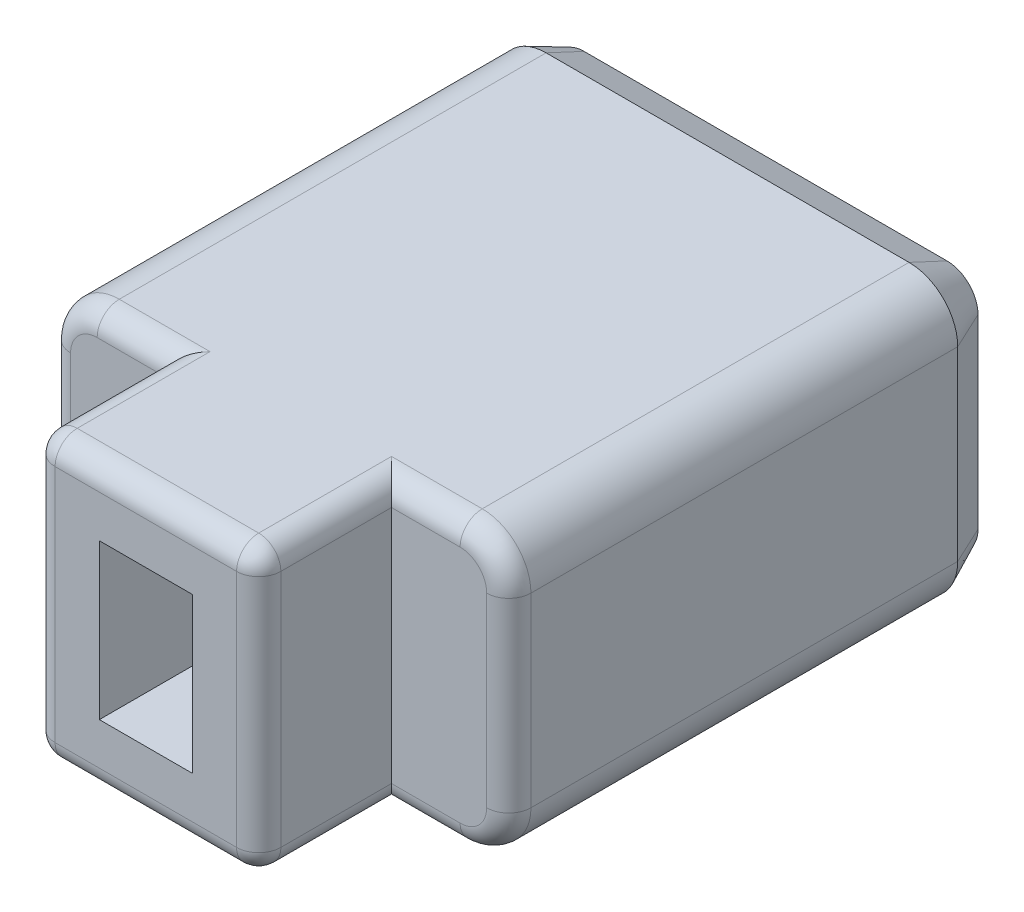
SolidWorks part; units mm, degrees
ref_plane "Plan de face" through (0, 0, 0) normal (0, 0, 1) x (1, 0, 0)
ref_plane "Plan de dessus" through (0, 0, 0) normal (0, 1, 0) x (1, 0, 0)
ref_plane "Plan de droite" through (0, 0, 0) normal (1, 0, 0) x (0, 0, -1)
sketch "Esquisse2" plane through (0, 0, 0) normal (0, 0, 1) x (1, 0, 0)
  line L1 (1.1, 0) -> (9.3, 0)
  line L2 (0, 1.1) -> (0, 5.3)
  line L3 (1.1, 6.4) -> (9.3, 6.4)
  line L4 (10.4, 1.1) -> (10.4, 5.3)
  arc A0 (9.3, 6.4) -> (10.4, 5.3) centre (9.3, 5.3) cw
  arc A1 (9.3, 0) -> (10.4, 1.1) centre (9.3, 1.1) ccw
  arc A2 (1.1, 0) -> (0, 1.1) centre (1.1, 1.1) cw
  arc A3 (0, 5.3) -> (1.1, 6.4) centre (1.1, 5.3) cw
  point P7 (10.4, 6.4)
  point P12 (0, 0)
  point P15 (0, 6.4)
  dimension "D3" = 1.1
  dimension "D1" = 10.4
  dimension "D2" = 6.4
extrude "Boss.-Extru.1" add sketch "Esquisse2" along normal blind 14
sketch "Esquisse3" plane through (0, 0, 14) normal (0, 0, 1) x (1, 0, 0)
  line L0 (0, 5.3) -> (0, 1.1) construction
  line L1 (4.15, 4.95) -> (6.25, 4.95)
  line L2 (4.15, 4.95) -> (4.15, 1.45)
  line L3 (4.15, 1.45) -> (6.25, 1.45)
  line L4 (6.25, 4.95) -> (6.25, 1.45)
  line L5 (10.4, 1.1) -> (10.4, 5.3) construction
  line L6 (9.3, 6.4) -> (1.1, 6.4) construction
  line L7 (1.1, 0) -> (9.3, 0) construction
  dimension "D1" = 2.1
  dimension "D2" = 3.5
  dimension "D3" = 4.15
  dimension "D4" = 4.15
  dimension "D5" = 1.45
  dimension "D6" = 1.45
extrude "Enlèv. mat.-Extru.1" cut sketch "Esquisse3" against normal blind 3
sketch "Esquisse4" plane through (0, 0, 14) normal (0, 0, 1) x (1, 0, 0)
  line L0 (2.65, 6.4) -> (2.65, 0)
  line L1 (9.3, 6.4) -> (1.1, 6.4) construction
  line L2 (1.1, 0) -> (9.3, 0) construction
  line L3 (2.65, 0) -> (7.75, 0)
  line L4 (7.75, 0) -> (7.75, 6.4)
  line L5 (7.75, 6.4) -> (2.65, 6.4)
  line L6 (4.15, 4.95) -> (4.15, 1.45) construction
  line L7 (6.25, 1.45) -> (6.25, 4.95) construction
  dimension "D1" = 1.5
  dimension "D2" = 1.5
extrude "Enlèv. mat.-Extru.2" cut sketch "Esquisse4" against normal blind 3 flip side to cut
fillet "Congé1" radius 0.5 18 edges at (8.525, 0, 11) (10.0778, 0.3222, 11) (10.4, 3.2, 11) (10.0778, 6.0778, 11) (1.875, 6.4, 11) (0.3222, 6.0778, 11) (1.875, 0, 11) (0.3222, 0.3222, 11) (7.75, 6.4, 12.5) (2.65, 6.4, 12.5) (7.75, 0, 12.5) (2.65, 0, 12.5) (2.65, 3.2, 14) (5.2, 6.4, 14) (7.75, 3.2, 14) (5.2, 0, 14) (8.525, 6.4, 11) (0, 3.2, 11)
chamfer "Chanfrein1" distance 0.4 angle 65 8 edges at (5.2, 0, 0) (10.0778, 0.3222, 0) (0.3222, 0.3222, 0) (10.4, 3.2, 0) (0, 3.2, 0) (10.0778, 6.0778, 0) (0.3222, 6.0778, 0) (5.2, 6.4, 0) first distance on face at (5.2, 3.2, 0)
sketch "Esquisse5" plane through (0, 0, 0) normal (0, 0, -1) x (-1, 0, 0)
  line L0 (-0.4, 5.3) -> (-10, 5.3) construction
  arc A0 (-9.3, 6) -> (-10, 5.3) centre (-9.3, 5.3) ccw construction
  text T0 "4" font "Century Gothic" height 4
extrude "Enlèv. mat.-Extru.3" cut sketch "Esquisse5" against normal blind 0.3
extrude "Boss.-Extru.2" add sketch "Esquisse5<2>" along normal blind 0.3 separate body
sketch "Esquisse5<2>" plane through (0, 0, 0) normal (0, 0, -1) x (-1, 0, 0) same geometry as "Esquisse5"
